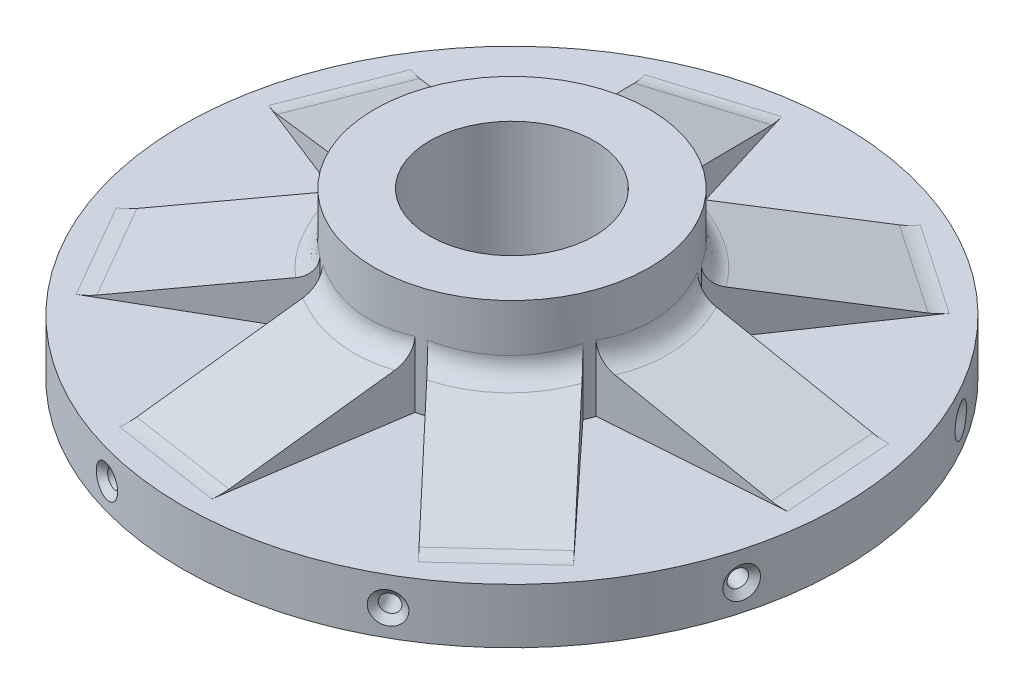
SolidWorks part; units mm, degrees
ref_plane "Front Plane" through (0, 0, 0) normal (0, 0, 1) x (1, 0, 0)
ref_plane "Top Plane" through (0, 0, 0) normal (0, 1, 0) x (1, 0, 0)
ref_plane "Right Plane" through (0, 0, 0) normal (1, 0, 0) x (0, 0, -1)
sketch "Sketch1" plane through (0, 0, 0) normal (0, 1, 0) x (1, 0, 0)
  circle A0 centre (0, 0) radius 30
  dimension "D1" = 60
extrude "Boss-Extrude1" add sketch "Sketch1" along normal mid plane 5
sketch "Sketch2" plane through (0, 2.5, 0) normal (0, 1, 0) x (1, 0, 0)
  circle A0 centre (0, 0) radius 12.5
  dimension "D1" = 25
extrude "Boss-Extrude2" add sketch "Sketch2" along normal blind 10
sketch "Sketch3" plane through (0, 12.5, 0) normal (0, 1, 0) x (1, 0, 0)
  circle A0 centre (0, 0) radius 7.5
  dimension "D1" = 15
extrude "Cut-Extrude1" cut sketch "Sketch3" against normal through all
ref_axis "Axis1" through (0, -2.5, 0) along (0, 1, 0)
ref_plane "Plane2" through (0, 0, 0) normal (0.5, 0, 0.866) x (0, 1, 0)
sketch "Sketch5" plane through (0, 0, 0) normal (0.5, 0, 0.866) x (0, 1, 0)
  line L0 (2.5, 7.5) -> (2.5, 27)
  line L1 (2.5, -30) -> (2.5, 30) construction
  line L2 (12.5, 7.5) -> (-2.5, 7.5) construction
  line L3 (2.5, 27) -> (8.0915, 7.5)
  line L4 (8.0915, 7.5) -> (2.5, 7.5)
  line L5 (-2.5, 0) -> (12.5, 0) construction
  line L6 (-2.5, 0) -> (27.5461, 0) construction
  line L7 (-2.5, 7.5) -> (-2.5, -7.5) construction
  dimension "D1" = 27
  dimension "D2" = 16
extrude "Boss-Extrude3" add sketch "Sketch5" along normal mid plane 10
pattern_circular "CirPattern1" count 7 over 360 about axis through (0, -2.5, 0) along (0, 1, 0) of "Boss-Extrude3"
fillet "Fillet1" radius 2 7 edges at (-1.863, 6.6578, 12.3604) (-10.8253, 6.6578, 6.25) (-11.6359, 6.6578, -4.5668) (-3.6844, 6.6578, -11.9447) (7.0415, 6.6578, -10.328) (12.465, 6.6578, -0.9341) (8.5022, 6.6578, 9.1631)
fillet "Fillet2" radius 5 7 edges at (18.3647, 2.5, 19.7924) (-4.0241, 2.5, 26.6984) (-23.3827, 2.5, 13.5) (-25.1336, 2.5, -9.8642) (-7.9584, 2.5, -25.8005) (15.2096, 2.5, -22.3084) (26.9245, 2.5, -2.0177)
hole_wizard "1/16 (0.0625) Diameter Hole1" positions "3DSketch1" profile "Sketch6" hole size "1/16" standard "ANSI Inch"
sketch3d "3DSketch1"
  point P0 (28.9182, -0.1102, 7.9835)
sketch "Sketch6" plane through (28.9182, -0.1102, 7.9835) normal (0, 1, 0) x (0.2661, 0, -0.9639)
  line L0 (0, 0) -> (0, 10.4769)
  line L1 (0, 10.4769) -> (0.7937, 10)
  line L2 (0.7937, 10) -> (0.7937, 0.5328)
  line L3 (0.7937, 0.5328) -> (1.4287, 0)
  line L5 (1.4287, 0) -> (0, 0)
  line L6 (-0.7937, 0.5328) -> (-1.4287, 0) construction
  line L10 (0, 10.4769) -> (-0.7938, 10) construction
  line L11 (0, -6.35) -> (0, 107.95) construction
  dimension "Hole Dia." = 1.5875
  dimension "Hole Depth" = 10
  dimension "Near C'Sink Dia." = 2.8575
  dimension "Near C'Sink Angle" = 100
  dimension "Drill Angle" = 118
pattern_circular "CirPattern2" count 8 over 360 about axis through (0, 2.5, 0) along (0, 1, 0) of "1/16 (0.0625) Diameter Hole1"
